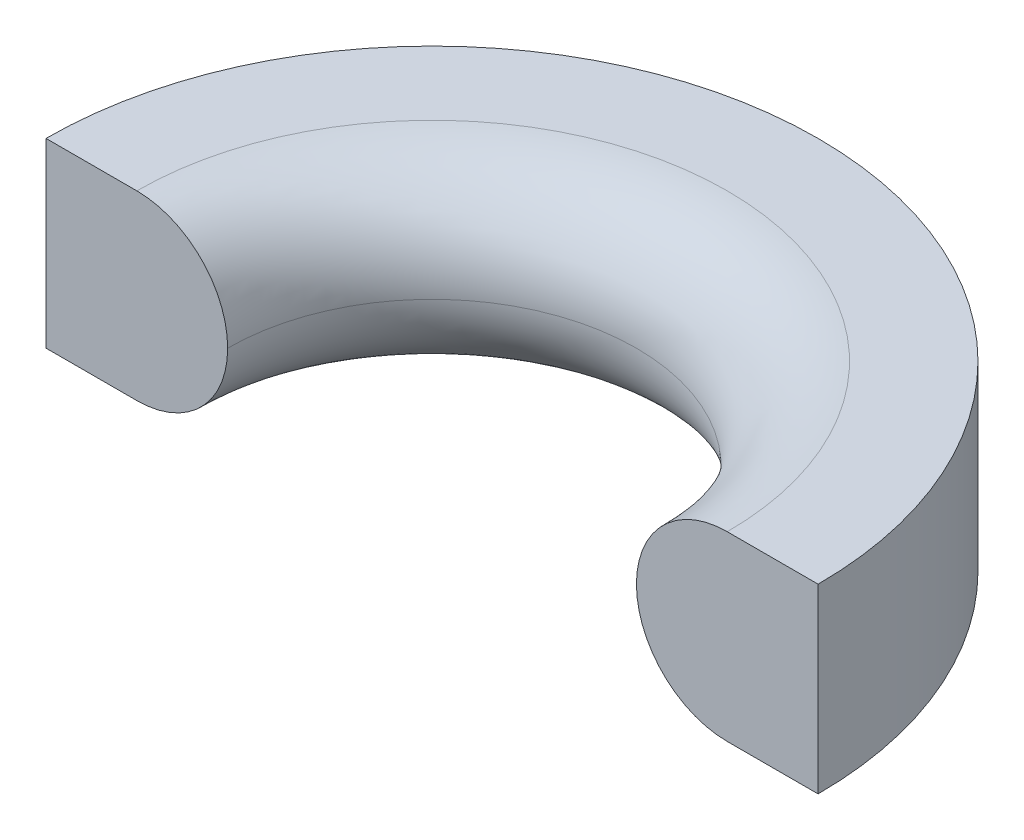
SolidWorks part; units mm, degrees
ref_plane "Front Plane" through (0, 0, 0) normal (0, 0, 1) x (1, 0, 0)
ref_plane "Top Plane" through (0, 0, 0) normal (0, 1, 0) x (1, 0, 0)
ref_plane "Right Plane" through (0, 0, 0) normal (1, 0, 0) x (0, 0, -1)
sketch "Sketch1" plane through (0, 0, 0) normal (0, 1, 0) x (1, 0, 0)
  line L0 (-4.25, 0) -> (-2.25, 0)
  line L1 (4.25, 0) -> (2.25, 0)
  arc A0 (-2.25, 0) -> (2.25, 0) centre (0, 0) cw
  arc A1 (-4.25, 0) -> (4.25, 0) centre (0, 0) cw
  dimension "D1" = 4.5
  dimension "D2" = 2
extrude "Boss-Extrude1" add sketch "Sketch1" along normal blind 2
fillet "Fillet1" radius 1 2 edges at (0, 0, -2.25) (0, 2, -2.25)
